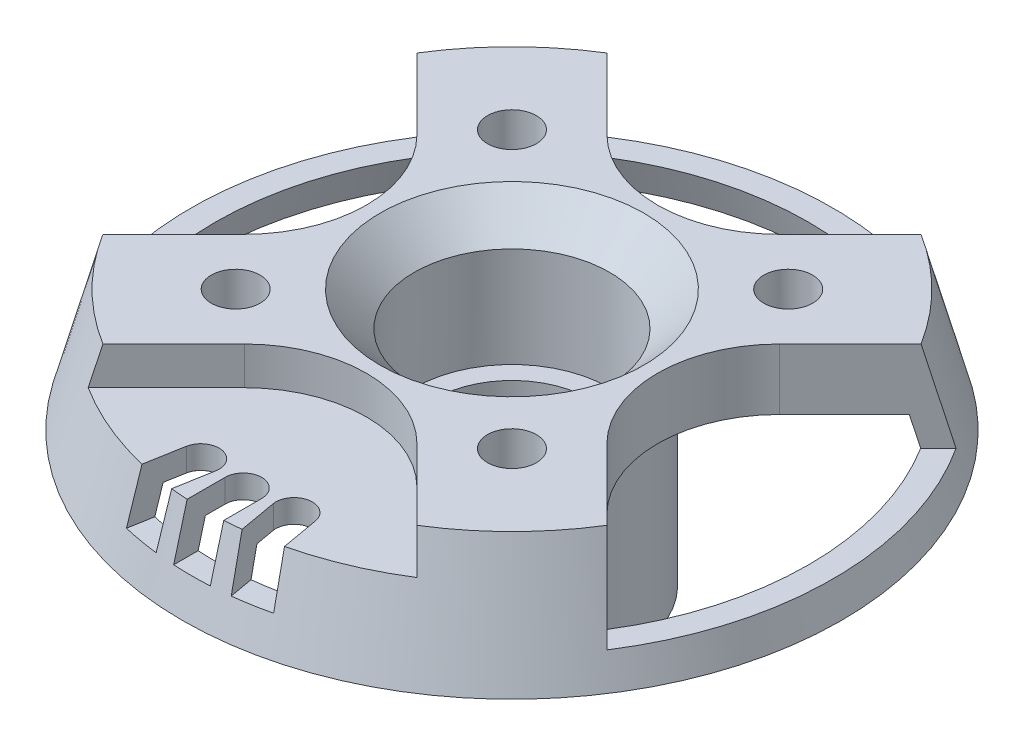
SolidWorks part; units mm, degrees
ref_plane "Front Plane" through (0, 0, 0) normal (0, 0, 1) x (1, 0, 0)
ref_plane "Top Plane" through (0, 0, 0) normal (0, 1, 0) x (1, 0, 0)
ref_plane "Right Plane" through (0, 0, 0) normal (1, 0, 0) x (0, 0, -1)
sketch "Sketch1" plane through (0, 0, 0) normal (0, 1, 0) x (1, 0, 0)
  circle A0 centre (0, 0) radius 13.5
  dimension "D1" = 27
extrude "Base size" add sketch "Sketch1" along normal blind 5
sketch "Sketch2" plane through (0, 5, 0) normal (0, 1, 0) x (1, 0, 0)
  line L0 (-9.5459, -9.5459) -> (9.5459, 9.5459) construction
  line L1 (-13.5, 0) -> (13.5, 0) construction
  line L2 (-9.5459, 9.5459) -> (9.5459, -9.5459) construction
  line L3 (0, 13.5) -> (0, -13.5) construction
  circle A0 centre (0, 0) radius 13.5 construction
  circle A1 centre (5.6569, 5.6569) radius 1
  circle A2 centre (-5.6569, -5.6569) radius 1
  circle A3 centre (5.6569, -5.6569) radius 1
  circle A4 centre (-5.6569, 5.6569) radius 1
  dimension "D2" = 2
  dimension "D1" = 45
  dimension "D3" = 16
extrude "Mounting holes" cut sketch "Sketch2" against normal up to next
sketch "Sketch3" plane through (0, 0, 0) normal (0, -1, 0) x (1, 0, 0)
  circle A0 centre (0, 0) radius 12.5
  circle A1 centre (0, 0) radius 13.5 construction
  dimension "D1" = 1
extrude "Rotor pocket" cut sketch "Sketch3" against normal blind 2.5 draft 15
chamfer "Outside chamfer" distance 5 angle 15 1 edges at (0, 5, 13.5) first distance on face at (0, 5, 13.5)
sketch "Sketch4" plane through (0, 5, 0) normal (0, 1, 0) x (1, 0, 0)
  line L0 (-8.5986, 8.5986) -> (8.5986, -8.5986) construction
  line L1 (-5.6569, 5.6569) -> (5.6569, 5.6569) construction
  line L2 (0, 12.1603) -> (0, -12.1603) construction
  line L3 (-12.1603, 0) -> (12.1603, 0) construction
  line L4 (-8.5986, -8.5986) -> (8.5986, 8.5986) construction
  line L5 (-10.5431, 6.6541) -> (6.6541, -10.5431)
  line L6 (-6.6541, -10.5431) -> (10.5431, 6.6541)
  line L7 (-6.6541, 10.5431) -> (10.5431, -6.6541)
  line L8 (-10.5431, -6.6541) -> (6.6541, 10.5431)
  line L9 (-10.5431, 6.6541) -> (-11.2903, 7.4012)
  line L10 (-6.6541, 10.5431) -> (-7.4012, 11.2903)
  line L11 (6.6541, 10.5431) -> (7.4012, 11.2903)
  line L12 (10.5431, 6.6541) -> (11.2903, 7.4012)
  line L13 (10.5431, -6.6541) -> (11.2903, -7.4012)
  line L14 (6.6541, -10.5431) -> (7.4012, -11.2903)
  line L15 (-6.6541, -10.5431) -> (-7.4012, -11.2903)
  line L16 (-10.5431, -6.6541) -> (-11.2903, -7.4012)
  circle A0 centre (0, 0) radius 12.1603 construction
  circle A1 centre (0, 0) radius 13.5
  circle A2 centre (0, 0) radius 13.5 construction
  circle M9 centre (0, 0) radius 12.1603
  dimension "D1" = 2.75
  dimension "D2" = 2.75
extrude "Bottom pockets top" cut sketch "Sketch4" against normal blind 1.55 contours L8 L5 M9 | L9 A1 L16 L8 L5 M9 | L7 L8 M9 | L11 A1 L10 L7 L8 M9 | L6 L7 M9 | L13 A1 L12 L6 L7 M9 | L15 A1 L14 L5 L6 M9 | L6 L5 M9 region at (-12.1626, 5, 0) region at (-8.9824, 5, 0) region at (0, 5, -8.9824) region at (0, 5, -12.1626) region at (0, 5, 8.9824) region at (0, 5, 12.1626) region at (8.9824, 5, 0) region at (12.1626, 5, 0)
sketch "Sketch5" plane through (0, 3.45, 0) normal (0, 1, 0) x (1, 0, 0)
  line L0 (-11.2903, 7.4012) -> (7.4012, -11.2903)
  line L1 (-10.3204, 6.4313) -> (-3.8891, 0) construction
  line L2 (7.4012, 11.2903) -> (-11.2903, -7.4012)
  line L3 (-10.3204, -6.4313) -> (-3.8891, 0) construction
  line L4 (-7.4012, 11.2903) -> (11.2903, -7.4012)
  line L5 (-6.4313, 10.3204) -> (0, 3.8891) construction
  line L6 (-7.4012, -11.2903) -> (11.2903, 7.4012)
  line L7 (3.8891, 0) -> (10.6216, 6.7325) construction
  circle A0 centre (0, 0) radius 13.5
  circle A1 centre (0, 0) radius 13.5 construction
  line M5 (-10.6216, -6.7325) -> (-3.8891, 0)
  line M6 (-3.8891, 0) -> (-10.6216, 6.7325)
  arc M7 (-10.6216, 6.7325) -> (-10.6216, -6.7325) centre (0, 0) ccw
extrude "Bottom pockets bottom" cut sketch "Sketch5" against normal offset from surface (2.15 mm away) 1.3 contours M7 M5 M6 | L0 A0 L2 M7 | L2 A0 L4 | L4 A0 L6 region at (-11.0626, 3.45, -6.9602) region at (-9.2333, 3.45, 0) region at (0, 3.45, -9.7912) region at (9.7912, 3.45, 0) up to face at (0, 0, -12.5)
fillet "Bottom pockets fillet" radius 5 4 edges at (0, 4.225, 3.8891) (3.8891, 3.75, 0) (0, 3.75, -3.8891) (-3.8891, 3.75, 0)
sketch "Sketch6" plane through (0, 5, 0) normal (0, 1, 0) x (1, 0, 0)
  circle A0 centre (0, 0) radius 4
  dimension "D1" = 8
extrude "Cut-Extrude5" cut sketch "Sketch6" against normal up to next
chamfer "Chamfer2" distance 1.4 angle 45 1 edges at (0, 5, 4)
sketch "Sketch7" plane through (0, 2.5, 0) normal (0, -1, 0) x (1, 0, 0)
  circle A0 centre (0, 0) radius 4
  circle A1 centre (0, 0) radius 4.8
  circle A2 centre (0, 0) radius 4 construction
  dimension "D1" = 0.8
extrude "Bearing bottom" add sketch "Sketch7" along normal blind 3
sketch "Sketch8" plane through (0, -0.5, 0) normal (0, -1, 0) x (1, 0, 0)
  circle A0 centre (0, 0) radius 4.8 construction
  circle A1 centre (0, 0) radius 4.8
  circle A2 centre (0, 0) radius 3.2
  circle A3 centre (0, 0) radius 4 construction
  dimension "D1" = 0.8
extrude "Bearing separator" add sketch "Sketch8" along normal blind 1
sketch "Sketch9" plane through (0, -1.5, 0) normal (0, -1, 0) x (1, 0, 0)
  circle A0 centre (0, 0) radius 4.8 construction
  circle A1 centre (0, 0) radius 4.8
  circle A2 centre (0, 0) radius 4 construction
  circle A3 centre (0, 0) radius 4
extrude "Bearing top" add sketch "Sketch9" along normal blind 4
sketch "Sketch10" plane through (0, 3.45, 0) normal (0, 1, 0) x (1, 0, 0)
  line L0 (0, -13.5) -> (0, 13.5) construction
  line L1 (0, 0) -> (0, -11) construction
  line L2 (0, 0) -> (-1.9101, -10.8329) construction
  line L3 (-2.6439, -10.6775) -> (-3.0788, -13.1442)
  line L4 (-1.1675, -10.9379) -> (-1.6025, -13.4046)
  line L5 (-0.75, -11) -> (-0.75, -13.4792)
  line L6 (2.6439, -10.6775) -> (3.0788, -13.1442)
  line L7 (1.1675, -10.9379) -> (1.6025, -13.4046)
  line L8 (0.75, -11) -> (0.75, -13.4792)
  circle A0 centre (0, 0) radius 11
  circle A1 centre (0, 0) radius 13.5 construction
  circle A2 centre (0, -11) radius 0.75
  circle A3 centre (-1.9101, -10.8329) radius 0.75
  circle A4 centre (1.9101, -10.8329) radius 0.75
  circle A5 centre (0, 0) radius 13.5
  arc M11 (-6.7325, -10.6216) -> (6.7325, -10.6216) centre (0, 0) ccw
  dimension "D1" = 2.5
  dimension "D2" = 1.5
  dimension "D4" = 10
  dimension "D3" = 2
extrude "Cut-Extrude6" cut sketch "Sketch10" against normal offset from surface (2.05 mm away) 1.4 contours A0 A3 | L3 A3 L4 A0 | A3 L3 L4 M11 | L3 A5 L4 M11 | L5 A5 L8 M11 | A2 L5 L8 M11 | A2 A0 | A0 A2 | A4 A0 | A4 L6 A0 L7 | L6 A4 L7 M11 | L7 A5 L6 M11 region at (-1.9646, 3.45, 11.1418) region at (-1.8541, 3.45, 10.5149) region at (-2.095, 3.45, 11.8813) region at (-2.2627, 3.45, 12.8326) region at (1.9646, 3.45, 11.1418) region at (1.8541, 3.45, 10.5149) region at (0, 3.45, 10.6771) region at (0, 3.45, 11.3137) region at (2.095, 3.45, 11.8813) region at (0, 3.45, 12.0643) region at (0, 3.45, 13.0306) region at (2.2627, 3.45, 12.8326) up to face at (0, 0, -12.5)
sketch "Sketch11" plane through (0, 5, 0) normal (0, 1, 0) x (1, 0, 0)
  line L0 (5.6569, -5.6569) -> (-5.6569, 5.6569) construction
  line L1 (5.6569, 5.6569) -> (-5.6569, -5.6569) construction
ref_axis "Center axis" through (0, 26.8978, 0) along (0, -1, 0)
